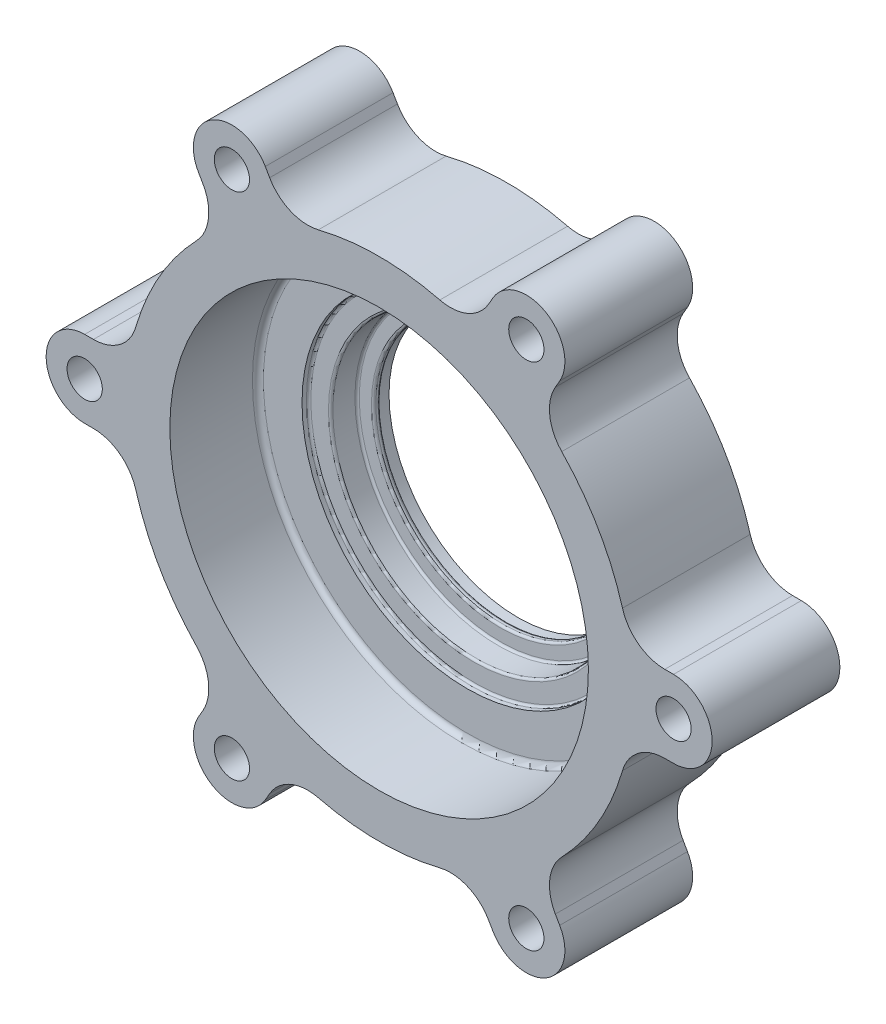
SolidWorks part; units mm, degrees
ref_plane "Front Plane" through (0, 0, 0) normal (0, 0, 1) x (1, 0, 0)
ref_plane "Top Plane" through (0, 0, 0) normal (0, 1, 0) x (1, 0, 0)
ref_plane "Right Plane" through (0, 0, 0) normal (1, 0, 0) x (0, 0, -1)
sketch "Sketch1" plane through (0, 0, 0) normal (0, 0, 1) x (1, 0, 0)
  line L0 (113.6607, 17.5) -> (133.6607, 17.5)
  line L1 (55, 0) -> (-55, 0) construction
  line L2 (113.6607, -17.5) -> (133.6607, -17.5)
  line L3 (71.9858, -89.683) -> (81.9858, -107.0035)
  line L4 (41.6749, -107.183) -> (51.6749, -124.5035)
  line L5 (-41.6749, -107.183) -> (-51.6749, -124.5035)
  line L6 (-71.9858, -89.683) -> (-81.9858, -107.0035)
  line L7 (-113.6607, -17.5) -> (-133.6607, -17.5)
  line L8 (-113.6607, 17.5) -> (-133.6607, 17.5)
  line L9 (-71.9858, 89.683) -> (-81.9858, 107.0035)
  line L10 (-41.6749, 107.183) -> (-51.6749, 124.5035)
  line L11 (41.6749, 107.183) -> (51.6749, 124.5035)
  line L12 (71.9858, 89.683) -> (81.9858, 107.0035)
  circle A0 centre (0, 0) radius 95
  circle A1 centre (0, 0) radius 115
  arc A2 (133.6607, 17.5) -> (133.6607, -17.5) centre (133.6607, 0) cw
  circle A3 centre (133.6607, 0) radius 8
  arc A4 (81.9858, -107.0035) -> (51.6749, -124.5035) centre (66.8303, -115.7535) cw
  circle A5 centre (66.8303, -115.7535) radius 8
  arc A6 (-51.6749, -124.5035) -> (-81.9858, -107.0035) centre (-66.8303, -115.7535) cw
  circle A7 centre (-66.8303, -115.7535) radius 8
  arc A8 (-133.6607, -17.5) -> (-133.6607, 17.5) centre (-133.6607, 0) cw
  circle A9 centre (-133.6607, 0) radius 8
  arc A10 (-81.9858, 107.0035) -> (-51.6749, 124.5035) centre (-66.8303, 115.7535) cw
  circle A11 centre (-66.8303, 115.7535) radius 8
  arc A12 (51.6749, 124.5035) -> (81.9858, 107.0035) centre (66.8303, 115.7535) cw
  circle A13 centre (66.8303, 115.7535) radius 8
  circle A14 centre (0, 0) radius 75
  point P45 (0, 0)
  dimension "D1" = 190
  dimension "D3" = 20
  dimension "D5" = 16
  dimension "D7" = 150
  dimension "D4" = 35
  dimension "D2" = 20
  dimension "D6" = 6
extrude "Boss-Extrude1" add sketch "Sketch1" along normal blind 58 contours A1 A0 | A8 L7 A1 L8 A9 | A10 L9 A1 L10 A11 | A12 L11 A1 L12 A13 | A2 L0 A1 L2 A3 | A4 L3 A1 L4 A5 | A6 L5 A1 L6 A7 region at (123.6607, 16.987, 0) region at (111.4215, 8.5274, 0) region at (57.8049, 100.121, 0) region at (76.4577, -98.6482, 0) region at (-57.8049, 100.121, 0) region at (-47.2029, -115.5384, 0) region at (-115.513, 0, 0)
fillet "Fillet5" radius 20 12 edges at (71.9858, 89.683, 29) (41.6749, 107.183, 29) (-41.6749, 107.183, 29) (-71.9858, 89.683, 29) (-113.6607, 17.5, 29) (-113.6607, -17.5, 29) (-71.9858, -89.683, 29) (-41.6749, -107.183, 29) (41.6749, -107.183, 29) (71.9858, -89.683, 29) (113.6607, -17.5, 29) (113.6607, 17.5, 29)
extrude "Boss-Extrude2" add sketch "Sketch1<3>" along normal blind 18 contours A0 A14 region at (-92.313, 0, 0)
sketch "Sketch1<3>" plane through (0, 0, 0) normal (0, 0, 1) x (1, 0, 0) same geometry as "Sketch1"
fillet "Fillet1" radius 2.5 1 edges at (95, 0, 18)
sketch "Sketch2" plane through (0, 0, 0) normal (0, 0, -1) x (-1, 0, 0)
  circle A0 centre (0, 0) radius 75
  circle A1 centre (0, 0) radius 65
  circle A2 centre (0, 0) radius 57.5
  circle M31 centre (0, 0) radius 75
  dimension "D1" = 130
  dimension "D2" = 115
extrude "Boss-Extrude3" add sketch "Sketch2" against normal blind 15 contours A1 M31 region at (72.8787, 0, 0)
extrude "Boss-Extrude4" add sketch "Sketch2<3>" against normal blind 3 contours A1 M31 | A1 A2 region at (72.8787, 0, 0) region at (63.1615, 0, 0)
sketch "Sketch2<3>" plane through (0, 0, 0) normal (0, 0, -1) x (-1, 0, 0) same geometry as "Sketch2"
fillet "Fillet3" radius 1 5 edges at (-75, 0, 15) (-65, 0, 15) (-57.5, 0, 0) (-57.5, 0, 3) (-65, 0, 3)
ref_axis "Axis1" through (0, 0, -8.15) along (0, 0, 1)
sketch "Sketch9" plane through (0, 0, 0) normal (0, 1, 0) x (1, 0, 0)
  line L0 (-58.5, 0) -> (-58.5, 5)
  line L1 (-58.5, 5) -> (-63.5, 5)
  line L2 (-63.5, 5) -> (-68.5, 0)
  line L3 (-68.5, 0) -> (-58.5, 0)
  dimension "D1" = 5
  dimension "D2" = 10
  dimension "D3" = 5
revolve "Revolve1" add sketch "Sketch9" angle 360 about axis through (0, 0, -8.15) along (0, 0, 1)
fillet "Fillet7" radius 1 1 edges at (-63.5, 0, -5)
